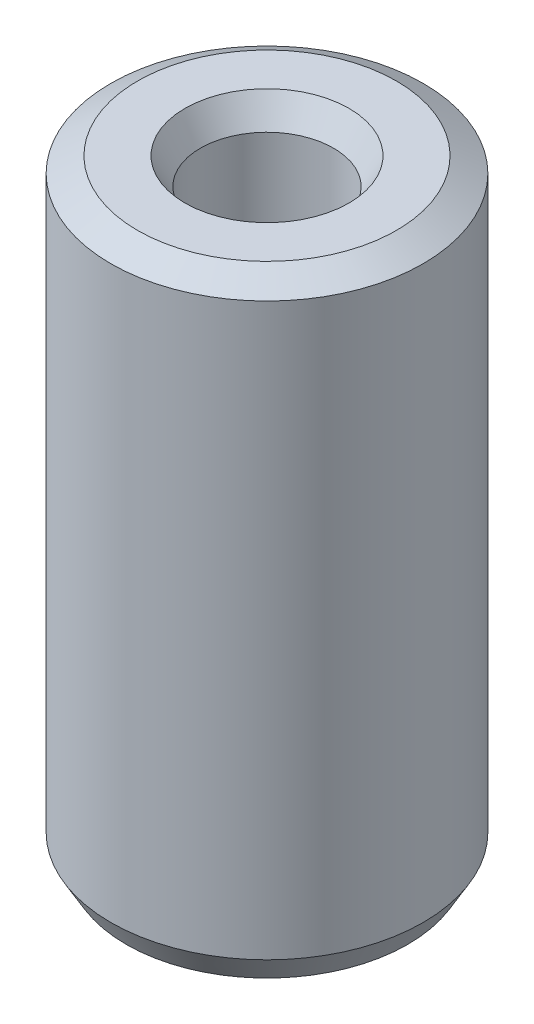
SolidWorks part; units mm, degrees
ref_plane "Front Plane" through (0, 0, 0) normal (0, 0, 1) x (1, 0, 0)
ref_plane "Top Plane" through (0, 0, 0) normal (0, 1, 0) x (1, 0, 0)
ref_plane "Right Plane" through (0, 0, 0) normal (1, 0, 0) x (0, 0, -1)
sketch "Sketch1" plane through (0, 0, 0) normal (0, 1, 0) x (1, 0, 0)
  circle A0 centre (0, 0) radius 10
  dimension "SLEEVE_OD" = 20
extrude "Boss-Extrude1" add sketch "Sketch1" along normal blind 39.2273
sketch "Sketch2" plane through (0, 0, 0) normal (0, 1, 0) x (1, 0, 0)
  circle A0 centre (0, 0) radius 4.2637
  dimension "BORE_D" = 8.5274
extrude "Cut-Extrude1" cut sketch "Sketch2" along normal through all
chamfer "Chamfer1" distance 0.9886 angle 60 4 edges at (0, 39.2273, 4.2637) (0, 0, 4.2637) (0, 0, 10) (0, 39.2273, 10) first distance on face at (0, 39.2273, 4.2637) first distance on face at (0, 0, 4.2637) first distance on face at (0, 39.2273, 10)
